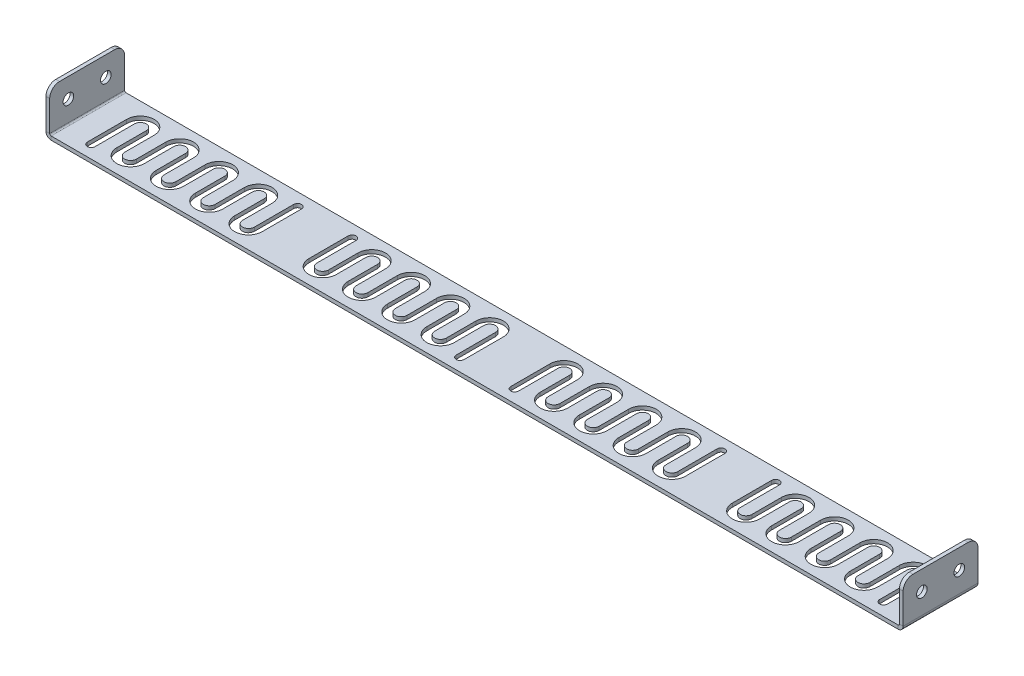
SolidWorks part; units mm, degrees
note: The reader was unsure of these and kept them because the rebuilt part matched: flange length of "Edge-Flange1".
ref_plane "Front Plane" through (0, 0, 0) normal (0, 0, 1) x (1, 0, 0)
ref_plane "Top Plane" through (0, 0, 0) normal (0, 1, 0) x (1, 0, 0)
ref_plane "Right Plane" through (0, 0, 0) normal (1, 0, 0) x (0, 0, -1)
sketch "Sketch14" plane through (0, 0, 0) normal (0, 1, 0) x (1, 0, 0)
  line L0 (436.24, -127.8892) -> (436.24, -130.1117) construction
  line L1 (0, 0) -> (436.24, 0)
  line L2 (0, 0) -> (0, 38.1)
  line L3 (0, 38.1) -> (436.24, 38.1)
  line L4 (436.24, 0) -> (436.24, 38.1)
  dimension "D1" = 38.1
base flange "Base-Flange1" sketch "Sketch14" thickness 1.88 reverse thickness direction no parameters "D1"=0.7366
edge flange "Edge-Flange1" sketch "Sketch21" flange profiles "Sketch21", "Sketch22" flange angle 90 flange length 23.038 flange position material inside bend radius 0.7366 thickness 1.88 relief rectangular parameters "D6"=10, "D8"=1
sketch "Sketch21" plane through (0, 0, 0) normal (-1, 0, 0) x (0, 0, 1)
  line L0 (264.9726, 21.158) -> (-133.8108, 21.158) construction
  line L2 (-38.1, 0) -> (-38.1, 21.158)
  line L3 (-38.1, 21.158) -> (0, 21.158)
  line L4 (0, 21.158) -> (0, 0)
  line L7 (-38.1, 0) -> (0, 0) construction
  line L8 (-38.1, 0) -> (0, 0)
sketch "Sketch22" plane through (436.24, 0, 0) normal (1, 0, 0) x (0, 0, -1)
  line L0 (0, 0) -> (38.1, 0) construction
  line L1 (0, 0) -> (38.1, 0)
  line L2 (0, 0) -> (0, 21.158)
  line L3 (0, 21.158) -> (38.1, 21.158)
  line L4 (38.1, 21.158) -> (38.1, 0)
  line L5 (133.8108, 21.158) -> (-264.9726, 21.158) construction
bend "EdgeBend1" bend radius 0.7366 bend angle 90 parameters "D5"=1
bend "EdgeBend2" bend radius 0.7366 bend angle 90 parameters "D5"=2
sketch "Sketch23" plane through (0, 0, 0) normal (-1, 0, 0) x (0, 0, 1)
  line L0 (-38.1, 11.158) -> (-19.05, 11.158) construction
  line L3 (-19.05, 13.3805) -> (-19.05, 8.9355) construction
  line L4 (127.8892, 13.3805) -> (-132.4608, 13.3805) construction
  line L5 (-132.4608, 8.9355) -> (127.8892, 8.9355) construction
  line L6 (-38.1, 21.158) -> (-38.1, 0.7366) construction
  line L7 (-19.05, 11.158) -> (0, 11.158) construction
  line L8 (0, 0.7366) -> (0, 21.158) construction
  circle A0 centre (-28.575, 11.158) radius 2.7051
  circle A1 centre (-9.525, 11.158) radius 2.7051
  point P6 (-19.05, 11.158)
  point P20 (-28.575, 11.158)
  dimension "D1" = 5.4102
extrude "Cut-Extrude1" cut sketch "Sketch23" against normal through all normal cut yes
fillet "Fillet1" radius 5 4 edges at (435.3, 21.158, -38.1) (435.3, 21.158, 0) (0.94, 21.158, -38.1) (0.94, 21.158, 0)
sketch "Sketch25" plane through (0, 0, 0) normal (0, 1, 0) x (1, 0, 0)
  line L0 (16.4925, 11.55) -> (16.4925, 26.55) construction
  line L1 (26.4925, 26.55) -> (26.4925, 11.55) construction
  line L2 (36.4925, 11.55) -> (36.4925, 26.55) construction
  line L3 (46.4925, 26.55) -> (46.4925, 11.55) construction
  line L4 (56.4925, 11.55) -> (56.4925, 26.55) construction
  line L5 (66.4925, 26.55) -> (66.4925, 11.55) construction
  line L6 (76.4925, 11.55) -> (76.4925, 26.55) construction
  line L7 (86.4925, 26.55) -> (86.4925, 11.55) construction
  line L8 (96.4925, 11.55) -> (96.4925, 26.55) construction
  line L9 (94.4925, 31.55) -> (94.4925, 26.55)
  line L10 (98.4925, 31.55) -> (98.4925, 26.55)
  line L11 (2.6166, 33.55) -> (433.6234, 33.55) construction
  line L12 (98.4925, 19.05) -> (110.3683, 19.05) construction
  line L13 (110.3683, 19.05) -> (122.2442, 19.05) construction
  line L14 (14.4925, 19.05) -> (2.6166, 19.05) construction
  line L15 (110.3683, 33.55) -> (110.3683, 4.55) construction
  line L16 (126.2442, 31.55) -> (126.2442, 26.55)
  line L17 (122.2442, 31.55) -> (122.2442, 26.55)
  line L18 (122.2442, 11.55) -> (122.2442, 26.55)
  line L19 (136.2442, 26.55) -> (136.2442, 11.55)
  line L20 (142.2442, 11.55) -> (142.2442, 26.55)
  line L21 (156.2442, 26.55) -> (156.2442, 11.55)
  line L22 (162.2442, 11.55) -> (162.2442, 26.55)
  line L23 (176.2442, 26.55) -> (176.2442, 11.55)
  line L24 (182.2442, 11.55) -> (182.2442, 26.55)
  line L25 (196.2442, 26.55) -> (196.2442, 11.55)
  line L26 (202.2442, 11.55) -> (202.2442, 26.55)
  line L27 (202.2442, 11.55) -> (202.2442, 6.55)
  line L28 (206.2442, 11.55) -> (206.2442, 6.55)
  line L29 (206.2442, 11.55) -> (206.2442, 26.55)
  line L30 (192.2442, 26.55) -> (192.2442, 11.55)
  line L31 (186.2442, 11.55) -> (186.2442, 26.55)
  line L32 (172.2442, 26.55) -> (172.2442, 11.55)
  line L33 (166.2442, 11.55) -> (166.2442, 26.55)
  line L34 (152.2442, 26.55) -> (152.2442, 11.55)
  line L35 (146.2442, 11.55) -> (146.2442, 26.55)
  line L36 (132.2442, 26.55) -> (132.2442, 11.55)
  line L37 (126.2442, 11.55) -> (126.2442, 26.55)
  line L38 (218.12, 33.55) -> (218.12, 4.55) construction
  line L39 (309.9959, 31.55) -> (309.9959, 26.55)
  line L40 (313.9959, 31.55) -> (313.9959, 26.55)
  line L41 (313.9959, 11.55) -> (313.9959, 26.55)
  line L42 (2.6166, 19.05) -> (433.6234, 19.05) construction
  line L43 (2.6166, 0) -> (2.6166, 38.1) construction
  line L44 (433.6234, 38.1) -> (433.6234, 0) construction
  line L45 (299.9959, 26.55) -> (299.9959, 11.55)
  line L46 (433.6234, 19.05) -> (421.7476, 19.05) construction
  line L47 (18.4925, 11.55) -> (18.4925, 26.55)
  line L48 (24.4925, 26.55) -> (24.4925, 11.55)
  line L49 (38.4925, 11.55) -> (38.4925, 26.55)
  line L50 (44.4925, 26.55) -> (44.4925, 11.55)
  line L51 (58.4925, 11.55) -> (58.4925, 26.55)
  line L52 (64.4925, 26.55) -> (64.4925, 11.55)
  line L53 (78.4925, 11.55) -> (78.4925, 26.55)
  line L54 (84.4925, 26.55) -> (84.4925, 11.55)
  line L55 (98.4925, 11.55) -> (98.4925, 26.55)
  line L89 (14.4925, 11.55) -> (14.4925, 26.55)
  line L90 (28.4925, 26.55) -> (28.4925, 11.55)
  line L91 (34.4925, 11.55) -> (34.4925, 26.55)
  line L92 (48.4925, 26.55) -> (48.4925, 11.55)
  line L93 (54.4925, 11.55) -> (54.4925, 26.55)
  line L94 (68.4925, 26.55) -> (68.4925, 11.55)
  line L95 (74.4925, 11.55) -> (74.4925, 26.55)
  line L96 (88.4925, 26.55) -> (88.4925, 11.55)
  line L97 (94.4925, 11.55) -> (94.4925, 26.55)
  line L131 (14.4925, 11.55) -> (14.4925, 6.55)
  line L132 (18.4925, 11.55) -> (18.4925, 6.55)
  line L133 (2.6166, 4.55) -> (433.6234, 4.55) construction
  line L136 (104.4925, 26.55) -> (104.4925, 11.55) construction
  line L137 (118.4925, 11.55) -> (118.4925, 26.55) construction
  line L138 (124.4925, 26.55) -> (124.4925, 11.55) construction
  line L139 (138.4925, 11.55) -> (138.4925, 26.55) construction
  line L140 (144.4925, 26.55) -> (144.4925, 11.55) construction
  line L141 (158.4925, 11.55) -> (158.4925, 26.55) construction
  line L142 (164.4925, 26.55) -> (164.4925, 11.55) construction
  line L143 (178.4925, 11.55) -> (178.4925, 26.55) construction
  line L144 (184.4925, 26.55) -> (184.4925, 11.55) construction
  line L145 (198.4925, 11.55) -> (198.4925, 26.55) construction
  line L146 (204.4925, 26.55) -> (204.4925, 11.55) construction
  line L147 (218.4925, 11.55) -> (218.4925, 26.55) construction
  line L148 (224.4925, 26.55) -> (224.4925, 11.55) construction
  line L149 (238.4925, 11.55) -> (238.4925, 26.55) construction
  line L150 (244.4925, 26.55) -> (244.4925, 11.55) construction
  line L151 (258.4925, 11.55) -> (258.4925, 26.55) construction
  line L152 (264.4925, 26.55) -> (264.4925, 11.55) construction
  line L153 (278.4925, 11.55) -> (278.4925, 26.55) construction
  line L154 (284.4925, 26.55) -> (284.4925, 11.55) construction
  line L155 (298.4925, 11.55) -> (298.4925, 26.55) construction
  line L156 (304.4925, 26.55) -> (304.4925, 11.55) construction
  line L157 (318.4925, 11.55) -> (318.4925, 26.55) construction
  line L158 (324.4925, 26.55) -> (324.4925, 11.55) construction
  line L159 (338.4925, 11.55) -> (338.4925, 26.55) construction
  line L160 (344.4925, 26.55) -> (344.4925, 11.55) construction
  line L161 (358.4925, 11.55) -> (358.4925, 26.55) construction
  line L162 (364.4925, 26.55) -> (364.4925, 11.55) construction
  line L163 (378.4925, 11.55) -> (378.4925, 26.55) construction
  line L164 (384.4925, 26.55) -> (384.4925, 11.55) construction
  line L165 (398.4925, 11.55) -> (398.4925, 26.55) construction
  line L166 (404.4925, 26.55) -> (404.4925, 11.55) construction
  line L167 (418.4925, 11.55) -> (418.4925, 26.55) construction
  line L168 (424.4925, 26.55) -> (424.4925, 11.55) construction
  line L169 (428.4925, 26.55) -> (428.4925, 11.55) construction
  line L170 (414.4925, 11.55) -> (414.4925, 26.55) construction
  line L171 (408.4925, 26.55) -> (408.4925, 11.55) construction
  line L172 (394.4925, 11.55) -> (394.4925, 26.55) construction
  line L173 (388.4925, 26.55) -> (388.4925, 11.55) construction
  line L174 (374.4925, 11.55) -> (374.4925, 26.55) construction
  line L175 (368.4925, 26.55) -> (368.4925, 11.55) construction
  line L176 (354.4925, 11.55) -> (354.4925, 26.55) construction
  line L177 (348.4925, 26.55) -> (348.4925, 11.55) construction
  line L178 (334.4925, 11.55) -> (334.4925, 26.55) construction
  line L179 (328.4925, 26.55) -> (328.4925, 11.55) construction
  line L180 (314.4925, 11.55) -> (314.4925, 26.55) construction
  line L181 (308.4925, 26.55) -> (308.4925, 11.55) construction
  line L182 (294.4925, 11.55) -> (294.4925, 26.55) construction
  line L183 (288.4925, 26.55) -> (288.4925, 11.55) construction
  line L184 (274.4925, 11.55) -> (274.4925, 26.55) construction
  line L185 (268.4925, 26.55) -> (268.4925, 11.55) construction
  line L186 (254.4925, 11.55) -> (254.4925, 26.55) construction
  line L187 (248.4925, 26.55) -> (248.4925, 11.55) construction
  line L188 (234.4925, 11.55) -> (234.4925, 26.55) construction
  line L189 (228.4925, 26.55) -> (228.4925, 11.55) construction
  line L190 (214.4925, 11.55) -> (214.4925, 26.55) construction
  line L191 (208.4925, 26.55) -> (208.4925, 11.55) construction
  line L192 (194.4925, 11.55) -> (194.4925, 26.55) construction
  line L193 (188.4925, 26.55) -> (188.4925, 11.55) construction
  line L194 (174.4925, 11.55) -> (174.4925, 26.55) construction
  line L195 (168.4925, 26.55) -> (168.4925, 11.55) construction
  line L196 (154.4925, 11.55) -> (154.4925, 26.55) construction
  line L197 (148.4925, 26.55) -> (148.4925, 11.55) construction
  line L198 (134.4925, 11.55) -> (134.4925, 26.55) construction
  line L199 (128.4925, 26.55) -> (128.4925, 11.55) construction
  line L200 (114.4925, 11.55) -> (114.4925, 26.55) construction
  line L201 (108.4925, 26.55) -> (108.4925, 11.55) construction
  line L202 (106.4925, 26.55) -> (106.4925, 11.55) construction
  line L203 (106.4925, 26.55) -> (106.4925, 11.55) construction
  line L204 (116.4925, 11.55) -> (116.4925, 26.55) construction
  line L205 (116.4925, 11.55) -> (116.4925, 26.55) construction
  line L206 (126.4925, 26.55) -> (126.4925, 11.55) construction
  line L207 (126.4925, 26.55) -> (126.4925, 11.55) construction
  line L208 (136.4925, 11.55) -> (136.4925, 26.55) construction
  line L209 (136.4925, 11.55) -> (136.4925, 26.55) construction
  line L210 (146.4925, 26.55) -> (146.4925, 11.55) construction
  line L211 (146.4925, 26.55) -> (146.4925, 11.55) construction
  line L212 (156.4925, 11.55) -> (156.4925, 26.55) construction
  line L213 (156.4925, 11.55) -> (156.4925, 26.55) construction
  line L214 (166.4925, 26.55) -> (166.4925, 11.55) construction
  line L215 (166.4925, 26.55) -> (166.4925, 11.55) construction
  line L216 (176.4925, 11.55) -> (176.4925, 26.55) construction
  line L217 (176.4925, 11.55) -> (176.4925, 26.55) construction
  line L218 (186.4925, 26.55) -> (186.4925, 11.55) construction
  line L219 (186.4925, 26.55) -> (186.4925, 11.55) construction
  line L220 (196.4925, 11.55) -> (196.4925, 26.55) construction
  line L221 (196.4925, 11.55) -> (196.4925, 26.55) construction
  line L222 (206.4925, 26.55) -> (206.4925, 11.55) construction
  line L223 (206.4925, 26.55) -> (206.4925, 11.55) construction
  line L224 (216.4925, 11.55) -> (216.4925, 26.55) construction
  line L225 (216.4925, 11.55) -> (216.4925, 26.55) construction
  line L226 (226.4925, 26.55) -> (226.4925, 11.55) construction
  line L227 (226.4925, 26.55) -> (226.4925, 11.55) construction
  line L228 (236.4925, 11.55) -> (236.4925, 26.55) construction
  line L229 (236.4925, 11.55) -> (236.4925, 26.55) construction
  line L230 (246.4925, 26.55) -> (246.4925, 11.55) construction
  line L231 (246.4925, 26.55) -> (246.4925, 11.55) construction
  line L232 (256.4925, 11.55) -> (256.4925, 26.55) construction
  line L233 (256.4925, 11.55) -> (256.4925, 26.55) construction
  line L234 (266.4925, 26.55) -> (266.4925, 11.55) construction
  line L235 (266.4925, 26.55) -> (266.4925, 11.55) construction
  line L236 (276.4925, 11.55) -> (276.4925, 26.55) construction
  line L237 (276.4925, 11.55) -> (276.4925, 26.55) construction
  line L238 (286.4925, 26.55) -> (286.4925, 11.55) construction
  line L239 (286.4925, 26.55) -> (286.4925, 11.55) construction
  line L240 (296.4925, 11.55) -> (296.4925, 26.55) construction
  line L241 (296.4925, 11.55) -> (296.4925, 26.55) construction
  line L242 (306.4925, 26.55) -> (306.4925, 11.55) construction
  line L243 (306.4925, 26.55) -> (306.4925, 11.55) construction
  line L244 (316.4925, 11.55) -> (316.4925, 26.55) construction
  line L245 (316.4925, 11.55) -> (316.4925, 26.55) construction
  line L246 (326.4925, 26.55) -> (326.4925, 11.55) construction
  line L247 (326.4925, 26.55) -> (326.4925, 11.55) construction
  line L248 (336.4925, 11.55) -> (336.4925, 26.55) construction
  line L249 (336.4925, 11.55) -> (336.4925, 26.55) construction
  line L250 (346.4925, 26.55) -> (346.4925, 11.55) construction
  line L251 (346.4925, 26.55) -> (346.4925, 11.55) construction
  line L252 (356.4925, 11.55) -> (356.4925, 26.55) construction
  line L253 (356.4925, 11.55) -> (356.4925, 26.55) construction
  line L254 (366.4925, 26.55) -> (366.4925, 11.55) construction
  line L255 (366.4925, 26.55) -> (366.4925, 11.55) construction
  line L256 (376.4925, 11.55) -> (376.4925, 26.55) construction
  line L257 (376.4925, 11.55) -> (376.4925, 26.55) construction
  line L258 (386.4925, 26.55) -> (386.4925, 11.55) construction
  line L259 (386.4925, 26.55) -> (386.4925, 11.55) construction
  line L260 (396.4925, 11.55) -> (396.4925, 26.55) construction
  line L261 (396.4925, 11.55) -> (396.4925, 26.55) construction
  line L262 (406.4925, 26.55) -> (406.4925, 11.55) construction
  line L263 (406.4925, 26.55) -> (406.4925, 11.55) construction
  line L264 (416.4925, 11.55) -> (416.4925, 26.55) construction
  line L265 (416.4925, 11.55) -> (416.4925, 26.55) construction
  line L266 (426.4925, 26.55) -> (426.4925, 11.55) construction
  line L267 (426.4925, 26.55) -> (426.4925, 11.55) construction
  line L268 (293.9959, 11.55) -> (293.9959, 26.55)
  line L269 (279.9959, 26.55) -> (279.9959, 11.55)
  line L270 (273.9959, 11.55) -> (273.9959, 26.55)
  line L271 (259.9959, 26.55) -> (259.9959, 11.55)
  line L272 (253.9959, 11.55) -> (253.9959, 26.55)
  line L273 (239.9959, 26.55) -> (239.9959, 11.55)
  line L274 (233.9959, 11.55) -> (233.9959, 26.55)
  line L275 (233.9959, 11.55) -> (233.9959, 6.55)
  line L276 (229.9959, 11.55) -> (229.9959, 6.55)
  line L277 (229.9959, 11.55) -> (229.9959, 26.55)
  line L278 (243.9959, 26.55) -> (243.9959, 11.55)
  line L279 (249.9959, 11.55) -> (249.9959, 26.55)
  line L280 (263.9959, 26.55) -> (263.9959, 11.55)
  line L281 (269.9959, 11.55) -> (269.9959, 26.55)
  line L282 (283.9959, 26.55) -> (283.9959, 11.55)
  line L283 (289.9959, 11.55) -> (289.9959, 26.55)
  line L284 (303.9959, 26.55) -> (303.9959, 11.55)
  line L285 (309.9959, 11.55) -> (309.9959, 26.55)
  line L286 (341.7476, 31.55) -> (341.7476, 26.55)
  line L287 (337.7476, 31.55) -> (337.7476, 26.55)
  line L288 (337.7476, 11.55) -> (337.7476, 26.55)
  line L289 (351.7476, 26.55) -> (351.7476, 11.55)
  line L290 (357.7476, 11.55) -> (357.7476, 26.55)
  line L291 (371.7476, 26.55) -> (371.7476, 11.55)
  line L292 (377.7476, 11.55) -> (377.7476, 26.55)
  line L293 (391.7476, 26.55) -> (391.7476, 11.55)
  line L294 (397.7476, 11.55) -> (397.7476, 26.55)
  line L295 (411.7476, 26.55) -> (411.7476, 11.55)
  line L296 (417.7476, 11.55) -> (417.7476, 26.55)
  line L297 (417.7476, 11.55) -> (417.7476, 6.55)
  line L298 (421.7476, 11.55) -> (421.7476, 6.55)
  line L299 (421.7476, 11.55) -> (421.7476, 26.55)
  line L300 (407.7476, 26.55) -> (407.7476, 11.55)
  line L301 (401.7476, 11.55) -> (401.7476, 26.55)
  line L302 (387.7476, 26.55) -> (387.7476, 11.55)
  line L303 (381.7476, 11.55) -> (381.7476, 26.55)
  line L304 (367.7476, 26.55) -> (367.7476, 11.55)
  line L305 (361.7476, 11.55) -> (361.7476, 26.55)
  line L306 (347.7476, 26.55) -> (347.7476, 11.55)
  line L307 (341.7476, 11.55) -> (341.7476, 26.55)
  line L308 (206.2442, 19.05) -> (218.12, 19.05) construction
  line L309 (218.12, 19.05) -> (229.9959, 19.05) construction
  line L310 (433.6234, 38.1) -> (2.6166, 38.1) construction
  arc A0 (26.4925, 26.55) -> (16.4925, 26.55) centre (21.4925, 26.55) ccw construction
  arc A1 (26.4925, 11.55) -> (36.4925, 11.55) centre (31.4925, 11.55) ccw construction
  arc A2 (46.4925, 26.55) -> (36.4925, 26.55) centre (41.4925, 26.55) ccw construction
  arc A3 (46.4925, 11.55) -> (56.4925, 11.55) centre (51.4925, 11.55) ccw construction
  arc A4 (66.4925, 26.55) -> (56.4925, 26.55) centre (61.4925, 26.55) ccw construction
  arc A5 (66.4925, 11.55) -> (76.4925, 11.55) centre (71.4925, 11.55) ccw construction
  arc A6 (86.4925, 26.55) -> (76.4925, 26.55) centre (81.4925, 26.55) ccw construction
  arc A7 (86.4925, 11.55) -> (96.4925, 11.55) centre (91.4925, 11.55) ccw construction
  arc A8 (98.4925, 31.55) -> (94.4925, 31.55) centre (96.4925, 31.55) ccw
  arc A9 (122.2442, 31.55) -> (126.2442, 31.55) centre (124.2442, 31.55) cw
  arc A10 (136.2442, 11.55) -> (122.2442, 11.55) centre (129.2442, 11.55) cw
  arc A11 (136.2442, 26.55) -> (142.2442, 26.55) centre (139.2442, 26.55) cw
  arc A12 (156.2442, 11.55) -> (142.2442, 11.55) centre (149.2442, 11.55) cw
  arc A13 (156.2442, 26.55) -> (162.2442, 26.55) centre (159.2442, 26.55) cw
  arc A14 (176.2442, 11.55) -> (162.2442, 11.55) centre (169.2442, 11.55) cw
  arc A15 (176.2442, 26.55) -> (182.2442, 26.55) centre (179.2442, 26.55) cw
  arc A16 (196.2442, 11.55) -> (182.2442, 11.55) centre (189.2442, 11.55) cw
  arc A17 (196.2442, 26.55) -> (202.2442, 26.55) centre (199.2442, 26.55) cw
  arc A18 (206.2442, 6.55) -> (202.2442, 6.55) centre (204.2442, 6.55) cw
  arc A19 (192.2442, 26.55) -> (206.2442, 26.55) centre (199.2442, 26.55) cw
  arc A20 (192.2442, 11.55) -> (186.2442, 11.55) centre (189.2442, 11.55) cw
  arc A21 (172.2442, 26.55) -> (186.2442, 26.55) centre (179.2442, 26.55) cw
  arc A22 (172.2442, 11.55) -> (166.2442, 11.55) centre (169.2442, 11.55) cw
  arc A23 (152.2442, 26.55) -> (166.2442, 26.55) centre (159.2442, 26.55) cw
  arc A24 (152.2442, 11.55) -> (146.2442, 11.55) centre (149.2442, 11.55) cw
  arc A25 (132.2442, 26.55) -> (146.2442, 26.55) centre (139.2442, 26.55) cw
  arc A26 (132.2442, 11.55) -> (126.2442, 11.55) centre (129.2442, 11.55) cw
  arc A27 (313.9959, 31.55) -> (309.9959, 31.55) centre (311.9959, 31.55) ccw
  arc A28 (299.9959, 11.55) -> (313.9959, 11.55) centre (306.9959, 11.55) ccw
  arc A29 (299.9959, 26.55) -> (293.9959, 26.55) centre (296.9959, 26.55) ccw
  arc A30 (279.9959, 11.55) -> (293.9959, 11.55) centre (286.9959, 11.55) ccw
  arc A31 (279.9959, 26.55) -> (273.9959, 26.55) centre (276.9959, 26.55) ccw
  arc A32 (259.9959, 11.55) -> (273.9959, 11.55) centre (266.9959, 11.55) ccw
  arc A33 (259.9959, 26.55) -> (253.9959, 26.55) centre (256.9959, 26.55) ccw
  arc A34 (239.9959, 11.55) -> (253.9959, 11.55) centre (246.9959, 11.55) ccw
  arc A35 (239.9959, 26.55) -> (233.9959, 26.55) centre (236.9959, 26.55) ccw
  arc A36 (229.9959, 6.55) -> (233.9959, 6.55) centre (231.9959, 6.55) ccw
  arc A37 (243.9959, 26.55) -> (229.9959, 26.55) centre (236.9959, 26.55) ccw
  arc A38 (243.9959, 11.55) -> (249.9959, 11.55) centre (246.9959, 11.55) ccw
  arc A39 (263.9959, 26.55) -> (249.9959, 26.55) centre (256.9959, 26.55) ccw
  arc A40 (263.9959, 11.55) -> (269.9959, 11.55) centre (266.9959, 11.55) ccw
  arc A41 (24.4925, 26.55) -> (18.4925, 26.55) centre (21.4925, 26.55) ccw
  arc A42 (426.4925, 11.55) -> (436.4925, 11.55) centre (431.4925, 11.55) ccw [skipped]
  arc A43 (24.4925, 11.55) -> (38.4925, 11.55) centre (31.4925, 11.55) ccw
  arc A44 (44.4925, 26.55) -> (38.4925, 26.55) centre (41.4925, 26.55) ccw
  arc A45 (44.4925, 11.55) -> (58.4925, 11.55) centre (51.4925, 11.55) ccw
  arc A46 (64.4925, 26.55) -> (58.4925, 26.55) centre (61.4925, 26.55) ccw
  arc A47 (64.4925, 11.55) -> (78.4925, 11.55) centre (71.4925, 11.55) ccw
  arc A48 (84.4925, 26.55) -> (78.4925, 26.55) centre (81.4925, 26.55) ccw
  arc A49 (84.4925, 11.55) -> (98.4925, 11.55) centre (91.4925, 11.55) ccw
  arc A83 (28.4925, 26.55) -> (14.4925, 26.55) centre (21.4925, 26.55) ccw
  arc A84 (28.4925, 11.55) -> (34.4925, 11.55) centre (31.4925, 11.55) ccw
  arc A85 (48.4925, 26.55) -> (34.4925, 26.55) centre (41.4925, 26.55) ccw
  arc A86 (48.4925, 11.55) -> (54.4925, 11.55) centre (51.4925, 11.55) ccw
  arc A87 (68.4925, 26.55) -> (54.4925, 26.55) centre (61.4925, 26.55) ccw
  arc A88 (68.4925, 11.55) -> (74.4925, 11.55) centre (71.4925, 11.55) ccw
  arc A89 (88.4925, 26.55) -> (74.4925, 26.55) centre (81.4925, 26.55) ccw
  arc A90 (88.4925, 11.55) -> (94.4925, 11.55) centre (91.4925, 11.55) ccw
  arc A126 (14.4925, 6.55) -> (18.4925, 6.55) centre (16.4925, 6.55) ccw
  arc A128 (104.4925, 26.55) -> (98.4925, 26.55) centre (101.4925, 26.55) ccw construction
  arc A129 (106.4925, 26.55) -> (96.4925, 26.55) centre (101.4925, 26.55) ccw construction
  arc A130 (106.4925, 26.55) -> (96.4925, 26.55) centre (101.4925, 26.55) ccw construction
  arc A131 (108.4925, 26.55) -> (94.4925, 26.55) centre (101.4925, 26.55) ccw construction
  arc A132 (104.4925, 11.55) -> (118.4925, 11.55) centre (111.4925, 11.55) ccw construction
  arc A133 (124.4925, 26.55) -> (118.4925, 26.55) centre (121.4925, 26.55) ccw construction
  arc A134 (124.4925, 11.55) -> (138.4925, 11.55) centre (131.4925, 11.55) ccw construction
  arc A135 (144.4925, 26.55) -> (138.4925, 26.55) centre (141.4925, 26.55) ccw construction
  arc A136 (144.4925, 11.55) -> (158.4925, 11.55) centre (151.4925, 11.55) ccw construction
  arc A137 (164.4925, 26.55) -> (158.4925, 26.55) centre (161.4925, 26.55) ccw construction
  arc A138 (164.4925, 11.55) -> (178.4925, 11.55) centre (171.4925, 11.55) ccw construction
  arc A139 (184.4925, 26.55) -> (178.4925, 26.55) centre (181.4925, 26.55) ccw construction
  arc A140 (184.4925, 11.55) -> (198.4925, 11.55) centre (191.4925, 11.55) ccw construction
  arc A141 (204.4925, 26.55) -> (198.4925, 26.55) centre (201.4925, 26.55) ccw construction
  arc A142 (204.4925, 11.55) -> (218.4925, 11.55) centre (211.4925, 11.55) ccw construction
  arc A143 (224.4925, 26.55) -> (218.4925, 26.55) centre (221.4925, 26.55) ccw construction
  arc A144 (224.4925, 11.55) -> (238.4925, 11.55) centre (231.4925, 11.55) ccw construction
  arc A145 (244.4925, 26.55) -> (238.4925, 26.55) centre (241.4925, 26.55) ccw construction
  arc A146 (244.4925, 11.55) -> (258.4925, 11.55) centre (251.4925, 11.55) ccw construction
  arc A147 (264.4925, 26.55) -> (258.4925, 26.55) centre (261.4925, 26.55) ccw construction
  arc A148 (264.4925, 11.55) -> (278.4925, 11.55) centre (271.4925, 11.55) ccw construction
  arc A149 (284.4925, 26.55) -> (278.4925, 26.55) centre (281.4925, 26.55) ccw construction
  arc A150 (284.4925, 11.55) -> (298.4925, 11.55) centre (291.4925, 11.55) ccw construction
  arc A151 (304.4925, 26.55) -> (298.4925, 26.55) centre (301.4925, 26.55) ccw construction
  arc A152 (304.4925, 11.55) -> (318.4925, 11.55) centre (311.4925, 11.55) ccw construction
  arc A153 (324.4925, 26.55) -> (318.4925, 26.55) centre (321.4925, 26.55) ccw construction
  arc A154 (324.4925, 11.55) -> (338.4925, 11.55) centre (331.4925, 11.55) ccw construction
  arc A155 (344.4925, 26.55) -> (338.4925, 26.55) centre (341.4925, 26.55) ccw construction
  arc A156 (344.4925, 11.55) -> (358.4925, 11.55) centre (351.4925, 11.55) ccw construction
  arc A157 (364.4925, 26.55) -> (358.4925, 26.55) centre (361.4925, 26.55) ccw construction
  arc A158 (364.4925, 11.55) -> (378.4925, 11.55) centre (371.4925, 11.55) ccw construction
  arc A159 (384.4925, 26.55) -> (378.4925, 26.55) centre (381.4925, 26.55) ccw construction
  arc A160 (384.4925, 11.55) -> (398.4925, 11.55) centre (391.4925, 11.55) ccw construction
  arc A161 (404.4925, 26.55) -> (398.4925, 26.55) centre (401.4925, 26.55) ccw construction
  arc A162 (404.4925, 11.55) -> (418.4925, 11.55) centre (411.4925, 11.55) ccw construction
  arc A163 (424.4925, 26.55) -> (418.4925, 26.55) centre (421.4925, 26.55) ccw construction
  arc A164 (428.4925, 26.55) -> (414.4925, 26.55) centre (421.4925, 26.55) ccw construction
  arc A165 (408.4925, 11.55) -> (414.4925, 11.55) centre (411.4925, 11.55) ccw construction
  arc A166 (408.4925, 26.55) -> (394.4925, 26.55) centre (401.4925, 26.55) ccw construction
  arc A167 (388.4925, 11.55) -> (394.4925, 11.55) centre (391.4925, 11.55) ccw construction
  arc A168 (388.4925, 26.55) -> (374.4925, 26.55) centre (381.4925, 26.55) ccw construction
  arc A169 (368.4925, 11.55) -> (374.4925, 11.55) centre (371.4925, 11.55) ccw construction
  arc A170 (368.4925, 26.55) -> (354.4925, 26.55) centre (361.4925, 26.55) ccw construction
  arc A171 (348.4925, 11.55) -> (354.4925, 11.55) centre (351.4925, 11.55) ccw construction
  arc A172 (348.4925, 26.55) -> (334.4925, 26.55) centre (341.4925, 26.55) ccw construction
  arc A173 (328.4925, 11.55) -> (334.4925, 11.55) centre (331.4925, 11.55) ccw construction
  arc A174 (328.4925, 26.55) -> (314.4925, 26.55) centre (321.4925, 26.55) ccw construction
  arc A175 (308.4925, 11.55) -> (314.4925, 11.55) centre (311.4925, 11.55) ccw construction
  arc A176 (308.4925, 26.55) -> (294.4925, 26.55) centre (301.4925, 26.55) ccw construction
  arc A177 (288.4925, 11.55) -> (294.4925, 11.55) centre (291.4925, 11.55) ccw construction
  arc A178 (288.4925, 26.55) -> (274.4925, 26.55) centre (281.4925, 26.55) ccw construction
  arc A179 (268.4925, 11.55) -> (274.4925, 11.55) centre (271.4925, 11.55) ccw construction
  arc A180 (268.4925, 26.55) -> (254.4925, 26.55) centre (261.4925, 26.55) ccw construction
  arc A181 (248.4925, 11.55) -> (254.4925, 11.55) centre (251.4925, 11.55) ccw construction
  arc A182 (248.4925, 26.55) -> (234.4925, 26.55) centre (241.4925, 26.55) ccw construction
  arc A183 (228.4925, 11.55) -> (234.4925, 11.55) centre (231.4925, 11.55) ccw construction
  arc A184 (228.4925, 26.55) -> (214.4925, 26.55) centre (221.4925, 26.55) ccw construction
  arc A185 (208.4925, 11.55) -> (214.4925, 11.55) centre (211.4925, 11.55) ccw construction
  arc A186 (208.4925, 26.55) -> (194.4925, 26.55) centre (201.4925, 26.55) ccw construction
  arc A187 (188.4925, 11.55) -> (194.4925, 11.55) centre (191.4925, 11.55) ccw construction
  arc A188 (188.4925, 26.55) -> (174.4925, 26.55) centre (181.4925, 26.55) ccw construction
  arc A189 (168.4925, 11.55) -> (174.4925, 11.55) centre (171.4925, 11.55) ccw construction
  arc A190 (168.4925, 26.55) -> (154.4925, 26.55) centre (161.4925, 26.55) ccw construction
  arc A191 (148.4925, 11.55) -> (154.4925, 11.55) centre (151.4925, 11.55) ccw construction
  arc A192 (148.4925, 26.55) -> (134.4925, 26.55) centre (141.4925, 26.55) ccw construction
  arc A193 (128.4925, 11.55) -> (134.4925, 11.55) centre (131.4925, 11.55) ccw construction
  arc A194 (128.4925, 26.55) -> (114.4925, 26.55) centre (121.4925, 26.55) ccw construction
  arc A195 (108.4925, 11.55) -> (114.4925, 11.55) centre (111.4925, 11.55) ccw construction
  arc A196 (106.4925, 11.55) -> (116.4925, 11.55) centre (111.4925, 11.55) ccw construction
  arc A197 (106.4925, 11.55) -> (116.4925, 11.55) centre (111.4925, 11.55) ccw construction
  arc A198 (126.4925, 26.55) -> (116.4925, 26.55) centre (121.4925, 26.55) ccw construction
  arc A199 (126.4925, 26.55) -> (116.4925, 26.55) centre (121.4925, 26.55) ccw construction
  arc A200 (126.4925, 11.55) -> (136.4925, 11.55) centre (131.4925, 11.55) ccw construction
  arc A201 (126.4925, 11.55) -> (136.4925, 11.55) centre (131.4925, 11.55) ccw construction
  arc A202 (146.4925, 26.55) -> (136.4925, 26.55) centre (141.4925, 26.55) ccw construction
  arc A203 (146.4925, 26.55) -> (136.4925, 26.55) centre (141.4925, 26.55) ccw construction
  arc A204 (146.4925, 11.55) -> (156.4925, 11.55) centre (151.4925, 11.55) ccw construction
  arc A205 (146.4925, 11.55) -> (156.4925, 11.55) centre (151.4925, 11.55) ccw construction
  arc A206 (166.4925, 26.55) -> (156.4925, 26.55) centre (161.4925, 26.55) ccw construction
  arc A207 (166.4925, 26.55) -> (156.4925, 26.55) centre (161.4925, 26.55) ccw construction
  arc A208 (166.4925, 11.55) -> (176.4925, 11.55) centre (171.4925, 11.55) ccw construction
  arc A209 (166.4925, 11.55) -> (176.4925, 11.55) centre (171.4925, 11.55) ccw construction
  arc A210 (186.4925, 26.55) -> (176.4925, 26.55) centre (181.4925, 26.55) ccw construction
  arc A211 (186.4925, 26.55) -> (176.4925, 26.55) centre (181.4925, 26.55) ccw construction
  arc A212 (186.4925, 11.55) -> (196.4925, 11.55) centre (191.4925, 11.55) ccw construction
  arc A213 (186.4925, 11.55) -> (196.4925, 11.55) centre (191.4925, 11.55) ccw construction
  arc A214 (206.4925, 26.55) -> (196.4925, 26.55) centre (201.4925, 26.55) ccw construction
  arc A215 (206.4925, 26.55) -> (196.4925, 26.55) centre (201.4925, 26.55) ccw construction
  arc A216 (206.4925, 11.55) -> (216.4925, 11.55) centre (211.4925, 11.55) ccw construction
  arc A217 (206.4925, 11.55) -> (216.4925, 11.55) centre (211.4925, 11.55) ccw construction
  arc A218 (226.4925, 26.55) -> (216.4925, 26.55) centre (221.4925, 26.55) ccw construction
  arc A219 (226.4925, 26.55) -> (216.4925, 26.55) centre (221.4925, 26.55) ccw construction
  arc A220 (226.4925, 11.55) -> (236.4925, 11.55) centre (231.4925, 11.55) ccw construction
  arc A221 (226.4925, 11.55) -> (236.4925, 11.55) centre (231.4925, 11.55) ccw construction
  arc A222 (246.4925, 26.55) -> (236.4925, 26.55) centre (241.4925, 26.55) ccw construction
  arc A223 (246.4925, 26.55) -> (236.4925, 26.55) centre (241.4925, 26.55) ccw construction
  arc A224 (246.4925, 11.55) -> (256.4925, 11.55) centre (251.4925, 11.55) ccw construction
  arc A225 (246.4925, 11.55) -> (256.4925, 11.55) centre (251.4925, 11.55) ccw construction
  arc A226 (266.4925, 26.55) -> (256.4925, 26.55) centre (261.4925, 26.55) ccw construction
  arc A227 (266.4925, 26.55) -> (256.4925, 26.55) centre (261.4925, 26.55) ccw construction
  arc A228 (266.4925, 11.55) -> (276.4925, 11.55) centre (271.4925, 11.55) ccw construction
  arc A229 (266.4925, 11.55) -> (276.4925, 11.55) centre (271.4925, 11.55) ccw construction
  arc A230 (286.4925, 26.55) -> (276.4925, 26.55) centre (281.4925, 26.55) ccw construction
  arc A231 (286.4925, 26.55) -> (276.4925, 26.55) centre (281.4925, 26.55) ccw construction
  arc A232 (286.4925, 11.55) -> (296.4925, 11.55) centre (291.4925, 11.55) ccw construction
  arc A233 (286.4925, 11.55) -> (296.4925, 11.55) centre (291.4925, 11.55) ccw construction
  arc A234 (306.4925, 26.55) -> (296.4925, 26.55) centre (301.4925, 26.55) ccw construction
  arc A235 (306.4925, 26.55) -> (296.4925, 26.55) centre (301.4925, 26.55) ccw construction
  arc A236 (306.4925, 11.55) -> (316.4925, 11.55) centre (311.4925, 11.55) ccw construction
  arc A237 (306.4925, 11.55) -> (316.4925, 11.55) centre (311.4925, 11.55) ccw construction
  arc A238 (326.4925, 26.55) -> (316.4925, 26.55) centre (321.4925, 26.55) ccw construction
  arc A239 (326.4925, 26.55) -> (316.4925, 26.55) centre (321.4925, 26.55) ccw construction
  arc A240 (326.4925, 11.55) -> (336.4925, 11.55) centre (331.4925, 11.55) ccw construction
  arc A241 (326.4925, 11.55) -> (336.4925, 11.55) centre (331.4925, 11.55) ccw construction
  arc A242 (346.4925, 26.55) -> (336.4925, 26.55) centre (341.4925, 26.55) ccw construction
  arc A243 (346.4925, 26.55) -> (336.4925, 26.55) centre (341.4925, 26.55) ccw construction
  arc A244 (346.4925, 11.55) -> (356.4925, 11.55) centre (351.4925, 11.55) ccw construction
  arc A245 (346.4925, 11.55) -> (356.4925, 11.55) centre (351.4925, 11.55) ccw construction
  arc A246 (366.4925, 26.55) -> (356.4925, 26.55) centre (361.4925, 26.55) ccw construction
  arc A247 (366.4925, 26.55) -> (356.4925, 26.55) centre (361.4925, 26.55) ccw construction
  arc A248 (366.4925, 11.55) -> (376.4925, 11.55) centre (371.4925, 11.55) ccw construction
  arc A249 (366.4925, 11.55) -> (376.4925, 11.55) centre (371.4925, 11.55) ccw construction
  arc A250 (386.4925, 26.55) -> (376.4925, 26.55) centre (381.4925, 26.55) ccw construction
  arc A251 (386.4925, 26.55) -> (376.4925, 26.55) centre (381.4925, 26.55) ccw construction
  arc A252 (386.4925, 11.55) -> (396.4925, 11.55) centre (391.4925, 11.55) ccw construction
  arc A253 (386.4925, 11.55) -> (396.4925, 11.55) centre (391.4925, 11.55) ccw construction
  arc A254 (406.4925, 26.55) -> (396.4925, 26.55) centre (401.4925, 26.55) ccw construction
  arc A255 (406.4925, 26.55) -> (396.4925, 26.55) centre (401.4925, 26.55) ccw construction
  arc A256 (406.4925, 11.55) -> (416.4925, 11.55) centre (411.4925, 11.55) ccw construction
  arc A257 (406.4925, 11.55) -> (416.4925, 11.55) centre (411.4925, 11.55) ccw construction
  arc A258 (426.4925, 26.55) -> (416.4925, 26.55) centre (421.4925, 26.55) ccw construction
  arc A259 (426.4925, 26.55) -> (416.4925, 26.55) centre (421.4925, 26.55) ccw construction
  arc A260 (283.9959, 26.55) -> (269.9959, 26.55) centre (276.9959, 26.55) ccw
  arc A261 (283.9959, 11.55) -> (289.9959, 11.55) centre (286.9959, 11.55) ccw
  arc A262 (303.9959, 26.55) -> (289.9959, 26.55) centre (296.9959, 26.55) ccw
  arc A263 (303.9959, 11.55) -> (309.9959, 11.55) centre (306.9959, 11.55) ccw
  arc A264 (337.7476, 31.55) -> (341.7476, 31.55) centre (339.7476, 31.55) cw
  arc A265 (351.7476, 11.55) -> (337.7476, 11.55) centre (344.7476, 11.55) cw
  arc A266 (351.7476, 26.55) -> (357.7476, 26.55) centre (354.7476, 26.55) cw
  arc A267 (371.7476, 11.55) -> (357.7476, 11.55) centre (364.7476, 11.55) cw
  arc A268 (371.7476, 26.55) -> (377.7476, 26.55) centre (374.7476, 26.55) cw
  arc A269 (391.7476, 11.55) -> (377.7476, 11.55) centre (384.7476, 11.55) cw
  arc A270 (391.7476, 26.55) -> (397.7476, 26.55) centre (394.7476, 26.55) cw
  arc A271 (411.7476, 11.55) -> (397.7476, 11.55) centre (404.7476, 11.55) cw
  arc A272 (411.7476, 26.55) -> (417.7476, 26.55) centre (414.7476, 26.55) cw
  arc A273 (421.7476, 6.55) -> (417.7476, 6.55) centre (419.7476, 6.55) cw
  arc A274 (407.7476, 26.55) -> (421.7476, 26.55) centre (414.7476, 26.55) cw
  arc A275 (407.7476, 11.55) -> (401.7476, 11.55) centre (404.7476, 11.55) cw
  arc A276 (387.7476, 26.55) -> (401.7476, 26.55) centre (394.7476, 26.55) cw
  arc A277 (387.7476, 11.55) -> (381.7476, 11.55) centre (384.7476, 11.55) cw
  arc A278 (367.7476, 26.55) -> (381.7476, 26.55) centre (374.7476, 26.55) cw
  arc A279 (367.7476, 11.55) -> (361.7476, 11.55) centre (364.7476, 11.55) cw
  arc A280 (347.7476, 26.55) -> (361.7476, 26.55) centre (354.7476, 26.55) cw
  arc A281 (347.7476, 11.55) -> (341.7476, 11.55) centre (344.7476, 11.55) cw
  point P7 (16.4925, 19.05)
  point P742 (0, 0)
  dimension "D2" = 10
  dimension "D3" = 15
  dimension "D4" = 2
  dimension "D5" = 2
  dimension "D1" = 21
extrude "Cut-Extrude3" cut sketch "Sketch25" against normal through all normal cut yes
sketch "Bend-Lines1" [suppressed] plane through (0, 0, 0) normal (0, 1, 0) x (1, 0, 0)
sketch "Bounding-Box1" [suppressed] plane through (0, 0, 0) normal (0, 1, 0) x (1, 0, 0)
sheet metal parameters "Sheet-Metal3" thickness 1.88 parameters "D1"=0.7366
flat pattern "Flat-Pattern3" [suppressed]
sketch "Bend-Lines2" plane through (0, 0, 0) normal (0, 1, 0) x (1, 0, 0)
sketch3d "Bounding-Box2" [suppressed]
  line L0 (-142.9155, 40.706, 0) -> (0, 40.706, 0) construction
  line L1 (-142.9155, 0, 0) -> (0, 0, 0) construction
  line L2 (-142.9155, 40.706, 0) -> (-142.9155, 0, 0) construction
  line L3 (0, 40.706, 0) -> (0, 0, 0) construction
sheet metal parameters "Sheet-Metal4" thickness 1.88 parameters "D1"=0.7366
flat pattern "Flat-Pattern3"
sketch "Bend-Lines2" plane through (0, 0, 0) normal (0, 1, 0) x (1, 0, 0)
  line L0 (434.7925, 0) -> (434.7925, 40.706) construction
  line L1 (1.4475, 40.706) -> (1.4475, 0) construction
  line L2 (434.7925, 0) -> (434.7925, 40.706) construction
  line L3 (1.4475, 40.706) -> (1.4475, 0) construction
sketch3d "Bounding-Box2" [suppressed]
  line L0 (456.3451, 40.706, 0) -> (-20.1051, 40.706, 0) construction
  line L1 (456.3451, 0, 0) -> (-20.1051, 0, 0) construction
  line L2 (456.3451, 40.706, 0) -> (456.3451, 0, 0) construction
  line L3 (-20.1051, 40.706, 0) -> (-20.1051, 0, 0) construction
bend of the flat pattern "Flatten-<EdgeBend1>1"
bend of the flat pattern "Flatten-<EdgeBend2>1"
sheet metal parameters "Sheet-Metal5" thickness 1.88 parameters "D1"=0.7366
flat pattern "Flat-Pattern3"
sketch "Bend-Lines2" plane through (0, 0, 0) normal (0, 1, 0) x (1, 0, 0)
  line L0 (434.7925, 0) -> (434.7925, 40.706) construction
  line L1 (1.4475, 40.706) -> (1.4475, 0) construction
  line L2 (434.7925, 0) -> (434.7925, 40.706) construction
  line L3 (1.4475, 40.706) -> (1.4475, 0) construction
sketch3d "Bounding-Box2" [suppressed]
  line L0 (-20.1431, 40.7058, 0) -> (456.3831, 40.706, 0) construction
  line L1 (-20.1431, 0, 0) -> (456.3831, 0.0002, 0) construction
  line L2 (-20.1431, 40.7058, 0) -> (-20.1431, 0, 0) construction
  line L3 (456.3831, 40.706, 0) -> (456.3831, 0.0002, 0) construction
bend of the flat pattern "Flatten-<EdgeBend1>1"
bend of the flat pattern "Flatten-<EdgeBend2>1"
sheet metal parameters "Sheet-Metal7" thickness 1.88 parameters "D1"=0.7366
flat pattern "Flat-Pattern3"
sketch "Bend-Lines2" plane through (0, 0, 0) normal (0, 1, 0) x (1, 0, 0)
  line L0 (434.7925, 0) -> (434.7925, 38.1) construction
  line L1 (1.4475, 38.1) -> (1.4475, 0) construction
  line L2 (434.7925, 0) -> (434.7925, 38.1) construction
  line L3 (1.4475, 38.1) -> (1.4475, 0) construction
sketch3d "Bounding-Box2" [suppressed]
  line L0 (-20.1431, 38.0998, 0) -> (456.3831, 38.1, 0) construction
  line L1 (-20.1431, 0, 0) -> (456.3831, 0.0002, 0) construction
  line L2 (-20.1431, 38.0998, 0) -> (-20.1431, 0, 0) construction
  line L3 (456.3831, 38.1, 0) -> (456.3831, 0.0002, 0) construction
bend of the flat pattern "Flatten-<EdgeBend1>1"
bend of the flat pattern "Flatten-<EdgeBend2>1"
